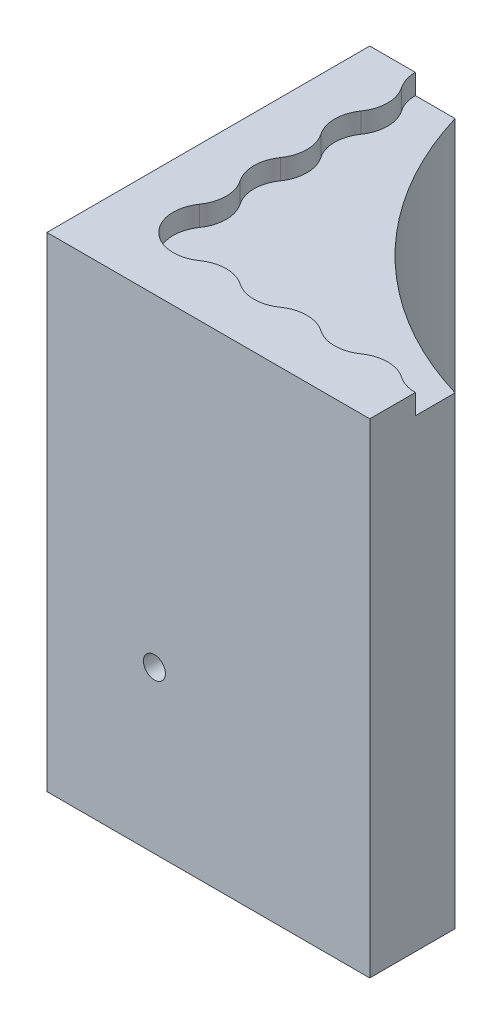
SolidWorks part; units mm, degrees
material "PET"
ref_plane "Front" through (0, 0, 0) normal (0, 0, 1) x (1, 0, 0)
ref_plane "Top" through (0, 0, 0) normal (0, 1, 0) x (1, 0, 0)
ref_plane "Right" through (0, 0, 0) normal (1, 0, 0) x (0, 0, -1)
sketch "Sketch1" plane through (0, 0, 0) normal (0, 1, 0) x (1, 0, 0)
  line L1 (0, 0) -> (50.8, 0)
  line L2 (0, 0) -> (0, 50.8)
  line L3 (0, 50.8) -> (50.8, 50.8)
  line L4 (50.8, 0) -> (50.8, 50.8)
  circle A0 centre (66.675, 66.675) radius 55.5625 construction
  dimension "D1" = 66.675
  dimension "D2" = 111.125
  dimension "D3" = 66.675
  dimension "D4" = 50.8
extrude "Boss-Extrude1" add sketch "Sketch1" along normal blind 76.2
sketch "Sketch2" plane through (0, 76.2, 0) normal (0, 1, 0) x (1, 0, 0)
  line L8 (129.2582, 124.9484) -> (133.499, 78.5045) construction
  line L9 (85.192, 137.4546) -> (125.4736, 129.1805) construction
  line L10 (129.2582, 124.9484) -> (133.499, 78.5045) construction
  line L11 (85.192, 137.4546) -> (125.4736, 129.1805) construction
  line L12 (130.017, 125.0177) -> (134.2578, 78.5738)
  line L13 (85.3453, 138.201) -> (125.6269, 129.9269)
  arc A0 (8.7916, 91.6214) -> (8.7916, 98.8786) centre (3.5805, 95.25) ccw construction
  arc A1 (8.7916, 91.6214) -> (8.7916, 86.1786) centre (12.7, 88.9) ccw construction
  arc A2 (8.7916, 78.9214) -> (8.7916, 86.1786) centre (3.5805, 82.55) ccw construction
  arc A3 (8.7916, 78.9214) -> (8.7796, 73.4959) centre (12.7, 76.2) ccw construction
  arc A4 (8.8014, 66.3169) -> (8.7796, 73.4959) centre (3.5524, 69.8905) ccw construction
  arc A5 (8.8014, 66.3169) -> (8.8053, 60.7032) centre (12.9199, 63.5129) ccw construction
  arc A6 (8.7834, 53.5096) -> (8.8053, 60.7032) centre (3.5613, 57.1223) ccw construction
  arc A7 (8.7834, 53.5096) -> (8.7916, 48.0786) centre (12.7, 50.8) ccw construction
  arc A8 (8.7916, 40.8214) -> (8.7916, 48.0786) centre (3.5805, 44.45) ccw construction
  arc A9 (8.7916, 40.8214) -> (8.7916, 35.3786) centre (12.7, 38.1) ccw construction
  arc A10 (8.7916, 28.1214) -> (8.7916, 35.3786) centre (3.5805, 31.75) ccw construction
  arc A11 (8.7916, 28.1214) -> (8.7916, 22.6786) centre (12.7, 25.4) ccw construction
  arc A12 (8.7916, 15.4214) -> (8.7916, 22.6786) centre (3.5805, 19.05) ccw construction
  arc A13 (8.7916, 15.4214) -> (15.4214, 8.7916) centre (12.7, 12.7) ccw construction
  arc A14 (22.6786, 8.7916) -> (15.4214, 8.7916) centre (19.05, 3.5805) ccw construction
  arc A15 (22.6786, 8.7916) -> (28.1214, 8.7916) centre (25.4, 12.7) ccw construction
  arc A16 (35.3786, 8.7916) -> (28.1214, 8.7916) centre (31.75, 3.5805) ccw construction
  arc A17 (35.3786, 8.7916) -> (40.8214, 8.7916) centre (38.1, 12.7) ccw construction
  arc A18 (48.0786, 8.7916) -> (40.8214, 8.7916) centre (44.45, 3.5805) ccw construction
  arc A19 (48.0786, 8.7916) -> (53.5096, 8.7834) centre (50.8, 12.7) ccw construction
  arc A20 (60.7032, 8.8053) -> (53.5096, 8.7834) centre (57.1223, 3.5613) ccw construction
  arc A21 (60.7032, 8.8053) -> (66.3169, 8.8014) centre (63.5129, 12.9199) ccw construction
  arc A22 (73.4959, 8.7796) -> (66.3169, 8.8014) centre (69.8905, 3.5524) ccw construction
  arc A23 (73.4959, 8.7796) -> (78.9214, 8.7916) centre (76.2, 12.7) ccw construction
  arc A24 (86.1786, 8.7916) -> (78.9214, 8.7916) centre (82.55, 3.5805) ccw construction
  arc A25 (86.1786, 8.7916) -> (91.6214, 8.7916) centre (88.9, 12.7) ccw construction
  arc A26 (98.8786, 8.7916) -> (91.6214, 8.7916) centre (95.25, 3.5805) ccw construction
  arc A27 (98.8786, 8.7916) -> (105.5642, 15.3394) centre (101.6, 12.7) ccw construction
  arc A28 (113.5841, 27.9306) -> (105.5642, 15.3394) centre (112.3572, 19.8624) ccw construction
  arc A29 (113.5841, 27.9306) -> (119.0625, 32.6538) centre (114.3, 32.639) ccw construction
  arc A30 (119.9168, 35.8549) -> (119.0625, 32.6538) centre (125.4124, 32.6736) ccw construction
  arc A31 (119.9168, 35.8549) -> (127.8227, 59.9277) centre (66.675, 66.675) ccw construction
  arc A32 (132.1466, 72.652) -> (127.8227, 59.9277) centre (158.75, 56.515) ccw construction
  arc A33 (132.1466, 72.652) -> (133.499, 78.5045) centre (123.9376, 77.6314) ccw construction
  arc A34 (129.2582, 124.9484) -> (125.4736, 129.1805) centre (124.5154, 124.5154) ccw construction
  arc A35 (85.192, 137.4546) -> (76.9535, 135.2891) centre (83.2602, 128.0498) ccw construction
  arc A36 (59.9277, 127.8227) -> (76.9535, 135.2891) centre (56.515, 158.75) ccw construction
  arc A37 (59.9277, 127.8227) -> (35.8549, 119.9168) centre (66.675, 66.675) ccw construction
  arc A38 (32.6538, 119.0625) -> (35.8549, 119.9168) centre (32.6736, 125.4124) ccw construction
  arc A39 (32.6538, 119.0625) -> (27.9306, 113.5841) centre (32.639, 114.3) ccw construction
  arc A40 (15.3394, 105.5642) -> (27.9306, 113.5841) centre (19.8624, 112.3572) ccw construction
  arc A41 (15.3394, 105.5642) -> (8.7916, 98.8786) centre (12.7, 101.6) ccw construction
  arc A42 (8.7916, 91.6214) -> (8.7916, 98.8786) centre (3.5805, 95.25) ccw construction
  arc A43 (8.7916, 91.6214) -> (8.7916, 86.1786) centre (12.7, 88.9) ccw construction
  arc A44 (8.7916, 78.9214) -> (8.7916, 86.1786) centre (3.5805, 82.55) ccw construction
  arc A45 (8.7916, 78.9214) -> (8.7796, 73.4959) centre (12.7, 76.2) ccw construction
  arc A46 (8.8014, 66.3169) -> (8.7796, 73.4959) centre (3.5524, 69.8905) ccw construction
  arc A47 (8.8014, 66.3169) -> (8.8053, 60.7032) centre (12.9199, 63.5129) ccw construction
  arc A48 (8.7834, 53.5096) -> (8.8053, 60.7032) centre (3.5613, 57.1223) ccw construction
  arc A49 (8.7834, 53.5096) -> (8.7916, 48.0786) centre (12.7, 50.8) ccw construction
  arc A50 (8.7916, 40.8214) -> (8.7916, 48.0786) centre (3.5805, 44.45) ccw construction
  arc A51 (8.7916, 40.8214) -> (8.7916, 35.3786) centre (12.7, 38.1) ccw construction
  arc A52 (8.7916, 28.1214) -> (8.7916, 35.3786) centre (3.5805, 31.75) ccw construction
  arc A53 (8.7916, 28.1214) -> (8.7916, 22.6786) centre (12.7, 25.4) ccw construction
  arc A54 (8.7916, 15.4214) -> (8.7916, 22.6786) centre (3.5805, 19.05) ccw construction
  arc A55 (8.7916, 15.4214) -> (15.4214, 8.7916) centre (12.7, 12.7) ccw construction
  arc A56 (22.6786, 8.7916) -> (15.4214, 8.7916) centre (19.05, 3.5805) ccw construction
  arc A57 (22.6786, 8.7916) -> (28.1214, 8.7916) centre (25.4, 12.7) ccw construction
  arc A58 (35.3786, 8.7916) -> (28.1214, 8.7916) centre (31.75, 3.5805) ccw construction
  arc A59 (35.3786, 8.7916) -> (40.8214, 8.7916) centre (38.1, 12.7) ccw construction
  arc A60 (48.0786, 8.7916) -> (40.8214, 8.7916) centre (44.45, 3.5805) ccw construction
  arc A61 (48.0786, 8.7916) -> (53.5096, 8.7834) centre (50.8, 12.7) ccw construction
  arc A62 (60.7032, 8.8053) -> (53.5096, 8.7834) centre (57.1223, 3.5613) ccw construction
  arc A63 (60.7032, 8.8053) -> (66.3169, 8.8014) centre (63.5129, 12.9199) ccw construction
  arc A64 (73.4959, 8.7796) -> (66.3169, 8.8014) centre (69.8905, 3.5524) ccw construction
  arc A65 (73.4959, 8.7796) -> (78.9214, 8.7916) centre (76.2, 12.7) ccw construction
  arc A66 (86.1786, 8.7916) -> (78.9214, 8.7916) centre (82.55, 3.5805) ccw construction
  arc A67 (86.1786, 8.7916) -> (91.6214, 8.7916) centre (88.9, 12.7) ccw construction
  arc A68 (98.8786, 8.7916) -> (91.6214, 8.7916) centre (95.25, 3.5805) ccw construction
  arc A69 (98.8786, 8.7916) -> (105.5642, 15.3394) centre (101.6, 12.7) ccw construction
  arc A70 (113.5841, 27.9306) -> (105.5642, 15.3394) centre (112.3572, 19.8624) ccw construction
  arc A71 (113.5841, 27.9306) -> (119.0625, 32.6538) centre (114.3, 32.639) ccw construction
  arc A72 (119.9168, 35.8549) -> (119.0625, 32.6538) centre (125.4124, 32.6736) ccw construction
  arc A73 (119.9168, 35.8549) -> (127.8227, 59.9277) centre (66.675, 66.675) ccw construction
  arc A74 (132.1466, 72.652) -> (127.8227, 59.9277) centre (158.75, 56.515) ccw construction
  arc A75 (132.1466, 72.652) -> (133.499, 78.5045) centre (123.9376, 77.6314) ccw construction
  arc A76 (129.2582, 124.9484) -> (125.4736, 129.1805) centre (124.5154, 124.5154) ccw construction
  arc A77 (85.192, 137.4546) -> (76.9535, 135.2891) centre (83.2602, 128.0498) ccw construction
  arc A78 (59.9277, 127.8227) -> (76.9535, 135.2891) centre (56.515, 158.75) ccw construction
  arc A79 (59.9277, 127.8227) -> (35.8549, 119.9168) centre (66.675, 66.675) ccw construction
  arc A80 (32.6538, 119.0625) -> (35.8549, 119.9168) centre (32.6736, 125.4124) ccw construction
  arc A81 (32.6538, 119.0625) -> (27.9306, 113.5841) centre (32.639, 114.3) ccw construction
  arc A82 (15.3394, 105.5642) -> (27.9306, 113.5841) centre (19.8624, 112.3572) ccw construction
  arc A83 (15.3394, 105.5642) -> (8.7916, 98.8786) centre (12.7, 101.6) ccw construction
  arc A84 (132.7981, 72.2568) -> (134.2578, 78.5738) centre (123.9376, 77.6314) ccw
  arc A85 (132.7981, 72.2568) -> (128.5801, 59.8441) centre (158.75, 56.515) ccw
  arc A86 (120.5763, 35.4731) -> (128.5801, 59.8441) centre (66.675, 66.675) ccw
  arc A87 (120.5763, 35.4731) -> (119.8245, 32.6562) centre (125.4124, 32.6736) ccw
  arc A88 (113.4695, 27.1773) -> (119.8245, 32.6562) centre (114.3, 32.639) ccw
  arc A89 (113.4695, 27.1773) -> (106.1985, 15.7617) centre (112.3572, 19.8624) ccw
  arc A90 (98.4431, 8.1663) -> (106.1985, 15.7617) centre (101.6, 12.7) ccw
  arc A91 (98.4431, 8.1663) -> (92.0569, 8.1663) centre (95.25, 3.5805) ccw
  arc A92 (85.7431, 8.1663) -> (92.0569, 8.1663) centre (88.9, 12.7) ccw
  arc A93 (85.7431, 8.1663) -> (79.3569, 8.1663) centre (82.55, 3.5805) ccw
  arc A94 (73.0633, 8.1523) -> (79.3569, 8.1663) centre (76.2, 12.7) ccw
  arc A95 (73.0633, 8.1523) -> (66.7457, 8.1715) centre (69.8905, 3.5524) ccw
  arc A96 (60.2735, 8.176) -> (66.7457, 8.1715) centre (63.5129, 12.9199) ccw
  arc A97 (60.2735, 8.176) -> (53.9431, 8.1568) centre (57.1223, 3.5613) ccw
  arc A98 (47.6431, 8.1663) -> (53.9431, 8.1568) centre (50.8, 12.7) ccw
  arc A99 (47.6431, 8.1663) -> (41.2569, 8.1663) centre (44.45, 3.5805) ccw
  arc A100 (34.9431, 8.1663) -> (41.2569, 8.1663) centre (38.1, 12.7) ccw
  arc A101 (34.9431, 8.1663) -> (28.5569, 8.1663) centre (31.75, 3.5805) ccw
  arc A102 (22.2431, 8.1663) -> (28.5569, 8.1663) centre (25.4, 12.7) ccw
  arc A103 (22.2431, 8.1663) -> (15.8569, 8.1663) centre (19.05, 3.5805) ccw
  arc A104 (8.1663, 15.8569) -> (15.8569, 8.1663) centre (12.7, 12.7) ccw
  arc A105 (8.1663, 15.8569) -> (8.1663, 22.2431) centre (3.5805, 19.05) ccw
  arc A106 (8.1663, 28.5569) -> (8.1663, 22.2431) centre (12.7, 25.4) ccw
  arc A107 (8.1663, 28.5569) -> (8.1663, 34.9431) centre (3.5805, 31.75) ccw
  arc A108 (8.1663, 41.2569) -> (8.1663, 34.9431) centre (12.7, 38.1) ccw
  arc A109 (8.1663, 41.2569) -> (8.1663, 47.6431) centre (3.5805, 44.45) ccw
  arc A110 (8.1568, 53.9431) -> (8.1663, 47.6431) centre (12.7, 50.8) ccw
  arc A111 (8.1568, 53.9431) -> (8.176, 60.2735) centre (3.5613, 57.1223) ccw
  arc A112 (8.1715, 66.7457) -> (8.176, 60.2735) centre (12.9199, 63.5129) ccw
  arc A113 (8.1715, 66.7457) -> (8.1523, 73.0633) centre (3.5524, 69.8905) ccw
  arc A114 (8.1663, 79.3569) -> (8.1523, 73.0633) centre (12.7, 76.2) ccw
  arc A115 (8.1663, 79.3569) -> (8.1663, 85.7431) centre (3.5805, 82.55) ccw
  arc A116 (8.1663, 92.0569) -> (8.1663, 85.7431) centre (12.7, 88.9) ccw
  arc A117 (8.1663, 92.0569) -> (8.1663, 98.4431) centre (3.5805, 95.25) ccw
  arc A118 (15.7617, 106.1985) -> (8.1663, 98.4431) centre (12.7, 101.6) ccw
  arc A119 (15.7617, 106.1985) -> (27.1773, 113.4695) centre (19.8624, 112.3572) ccw
  arc A120 (32.6562, 119.8245) -> (27.1773, 113.4695) centre (32.639, 114.3) ccw
  arc A121 (32.6562, 119.8245) -> (35.4731, 120.5763) centre (32.6736, 125.4124) ccw
  arc A122 (59.8441, 128.5801) -> (35.4731, 120.5763) centre (66.675, 66.675) ccw
  arc A123 (59.8441, 128.5801) -> (76.4529, 135.8637) centre (56.515, 158.75) ccw
  arc A124 (85.3453, 138.201) -> (76.4529, 135.8637) centre (83.2602, 128.0498) ccw
  arc A125 (130.017, 125.0177) -> (125.6269, 129.9269) centre (124.5154, 124.5154) ccw
  dimension "D1" = 0.762
extrude "Cut-Extrude1" cut sketch "Sketch2" against normal blind 3.175
sketch "Sketch3" plane through (0, 76.2, 0) normal (0, 1, 0) x (1, 0, 0)
  circle A0 centre (66.675, 66.675) radius 55.5625 construction
  circle A1 centre (66.675, 66.675) radius 55.5625
extrude "Cut-Extrude2" cut sketch "Sketch3" against normal through all
hole_wizard "#8-32 Tapped Hole1" positions "Sketch4" profile "Sketch5" tap size "#8-32" standard "ANSI Inch"
sketch "Sketch4" plane through (393.7, -15.875, 0) normal (0, 0, 1) x (1, 0, 0)
  point P30 (-376.782, 41.275)
  point P32 (-376.782, 41.275)
sketch "Sketch5" plane through (16.918, 25.4, 0) normal (1, 0, 0) x (0, -1, 0)
  line L0 (0, 0) -> (0, 11.7464)
  line L1 (0, 11.7464) -> (1.7272, 10.7086)
  line L2 (1.7272, 10.7086) -> (1.7272, 0)
  line L3 (1.7272, 0) -> (0, 0)
  line L4 (0, 11.7464) -> (-1.7272, 10.7086) construction
  line L5 (0, -6.35) -> (0, 107.95) construction
  dimension "Tap Drill Dia." = 3.4544
  dimension "Tap Drill Depth" = 10.7086
  dimension "Drill Angle" = 118
hole_wizard "#8-32 Tapped Hole2" positions "Sketch6" profile "Sketch7" tap size "#8-32" standard "ANSI Inch"
sketch "Sketch6" plane through (0, -15.875, -393.7) normal (-1, 0, 0) x (0, 0, 1)
  point P36 (374.968, 41.275)
  point P38 (374.968, 41.275)
sketch "Sketch7" plane through (0, 25.4, -18.732) normal (0, 1, 0) x (0, 0, 1)
  line L0 (0, 0) -> (0, 11.7464)
  line L1 (0, 11.7464) -> (1.7272, 10.7086)
  line L2 (1.7272, 10.7086) -> (1.7272, 0)
  line L3 (1.7272, 0) -> (0, 0)
  line L4 (0, 11.7464) -> (-1.7272, 10.7086) construction
  line L5 (0, -6.35) -> (0, 107.95) construction
  dimension "Tap Drill Dia." = 3.4544
  dimension "Tap Drill Depth" = 10.7086
  dimension "Drill Angle" = 118
